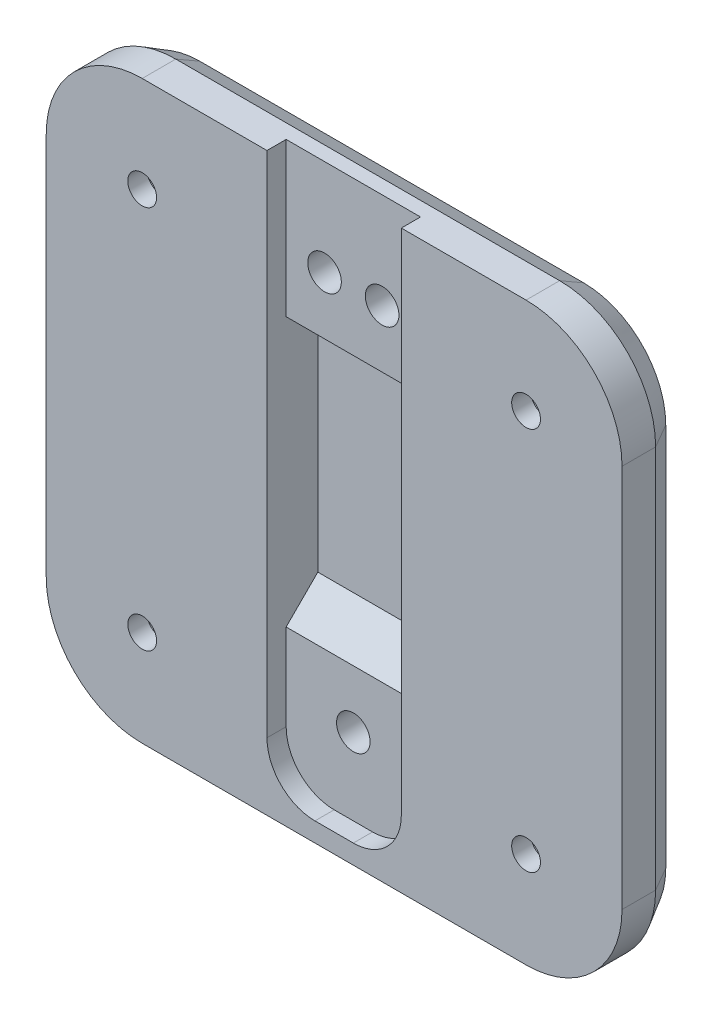
SolidWorks part; units mm, degrees
ref_plane "Front Plane" through (0, 0, 0) normal (0, 0, 1) x (1, 0, 0)
ref_plane "Top Plane" through (0, 0, 0) normal (0, 1, 0) x (1, 0, 0)
ref_plane "Right Plane" through (0, 0, 0) normal (1, 0, 0) x (0, 0, -1)
sketch "Sketch1" plane through (0, 0, 0) normal (0, 0, 1) x (1, 0, 0)
  line L1 (-20, 30) -> (20, 30)
  line L2 (-30, 20) -> (-30, -20)
  line L3 (-20, -30) -> (20, -30)
  line L4 (30, 20) -> (30, -20)
  arc A0 (20, 30) -> (30, 20) centre (20, 20) cw
  arc A1 (20, -30) -> (30, -20) centre (20, -20) ccw
  arc A2 (-30, -20) -> (-20, -30) centre (-20, -20) ccw
  arc A3 (-30, 20) -> (-20, 30) centre (-20, 20) cw
  point P6 (30, 30)
  point P11 (-30, -30)
  point P14 (-30, 30)
  point P15 (0, 30)
  point P17 (-30, 0)
  dimension "D3" = 10
  dimension "D1" = 60
  dimension "D2" = 60
extrude "Boss-Extrude1" add sketch "Sketch1" along normal blind 6
chamfer "Chamfer1" distance 2.5 angle 30 8 edges at (0, -30, 0) (27.0711, -27.0711, 0) (-27.0711, -27.0711, 0) (30, 0, 0) (-30, 0, 0) (27.0711, 27.0711, 0) (-27.0711, 27.0711, 0) (0, 30, 0) first distance on face at (0, -30, 3) first distance on face at (26.0355, -26.0355, 3) first distance on face at (-26.0355, -26.0355, 3) first distance on face at (30, 0, 3) first distance on face at (-30, 0, 3) first distance on face at (26.0355, 26.0355, 3) first distance on face at (-26.0355, 26.0355, 3) first distance on face at (0, 30, 3)
sketch "Sketch2" plane through (0, 0, 0) normal (0, 1, 0) x (1, 0, 0)
  line L4 (20, -6) -> (-20, -6) construction
  line L5 (-7, -10.8924) -> (7, -10.8924)
  line L6 (-7, -10.8924) -> (-7, -4)
  line L7 (-7, -4) -> (7, -4)
  line L8 (7, -10.8924) -> (7, -4)
  point P4 (0, -4)
  dimension "D1" = 14
  dimension "D2" = 2
extrude "Cut-Extrude1" cut sketch "Sketch2" against normal blind 28 and the other way through all
sketch "Sketch3" plane through (0, 0, 4) normal (0, 0, 1) x (1, 0, 0)
  line L0 (7, -28) -> (7, 30) construction
  line L1 (7, -10) -> (-7, -10)
  line L2 (7, -10) -> (7, 10)
  line L3 (7, 10) -> (-7, 10)
  line L4 (-7, -10) -> (-7, 10)
  line L5 (-7, 30) -> (-7, -28) construction
  point P8 (7, 0)
  dimension "D1" = 20
extrude "Cut-Extrude2" cut sketch "Sketch3" against normal blind 3.3
chamfer "Chamfer2" distance 4 angle 45 2 edges at (0, 10, 4) (0, -10, 4)
hole_wizard "Hole1" positions "Sketch4" profile "Sketch5" legacy end condition through all
sketch "Sketch4" plane through (0, 0, 0) normal (0, 0, -1) x (-1, 0, 0)
  line L0 (20, -20) -> (-20, -20) construction
  line L1 (-20, -20) -> (-20, 20) construction
  point P0 (20, -20)
  point P2 (-20, -20)
  point P4 (-20, 20)
  point P6 (20, 20)
  point P14 (-20, 0)
  point P16 (0, -20)
  dimension "D1" = 40
  dimension "D2" = 40
sketch "Sketch5" plane through (-20, -20, 0) normal (1, 0, 0) x (0, 1, 0)
  line L0 (0, 0) -> (0, 6)
  line L1 (0, 6) -> (1.5, 6)
  line L2 (1.5, 6) -> (1.5, 4)
  line L3 (1.5, 4) -> (2.05, 4)
  line L4 (2.05, 4) -> (2.05, 0)
  line L5 (2.05, 0) -> (0, 0)
  line L6 (0, 110) -> (0, -10) construction
  dimension "Diameter" = 3
  dimension "Depth" = 6
  dimension "C-Bore Diameter" = 4.1
  dimension "C-Bore Depth" = 4
hole_wizard "Hole2" positions "Sketch6" profile "Sketch7" legacy end condition through all
sketch "Sketch6" plane through (0, 0, 4) normal (0, 0, 1) x (1, 0, 0)
  line L1 (7, 30) -> (-7, 30) construction
  line L3 (-7, -28) -> (-7, -14) construction
  line L4 (7, -30) -> (-7, -30) construction
  line L5 (-7, 14) -> (-7, 30) construction
  line L6 (7, 14) -> (7, 30) construction
  point P0 (3, 20)
  point P2 (-3, 20)
  point P6 (0, -20)
  dimension "D1" = 10
  dimension "D2" = 10
  dimension "D3" = 4
  dimension "D4" = 7
  dimension "D5" = 4
sketch "Sketch7" plane through (3, 20, 4) normal (1, 0, 0) x (0, -1, 0)
  line L0 (0, 0) -> (0, 4)
  line L1 (0, 4) -> (1.5, 4)
  line L2 (1.5, 4) -> (1.5, 20)
  line L3 (1.5, 20) -> (1.75, 20)
  line L4 (1.75, 20) -> (1.75, 0)
  line L5 (1.75, 0) -> (0, 0)
  line L6 (0, 110) -> (0, -10) construction
  dimension "Diameter" = 3
  dimension "Depth" = 4
  dimension "C-Bore Diameter" = 3.5
  dimension "C-Bore Depth" = 20
fillet "Fillet2" radius 5 2 edges at (7, -28, 5) (-7, -28, 5)
chamfer "Chamfer3" distance 2 angle 15 4 edges at (-22.05, 20, 0) (-22.05, -20, 0) (17.95, 20, 0) (17.95, -20, 0) first distance on face at (-22.05, 20, 4) first distance on face at (-22.05, -20, 4) first distance on face at (17.95, 20, 4) first distance on face at (17.95, -20, 4)
fillet "Fillet3" [suppressed] radius 3
